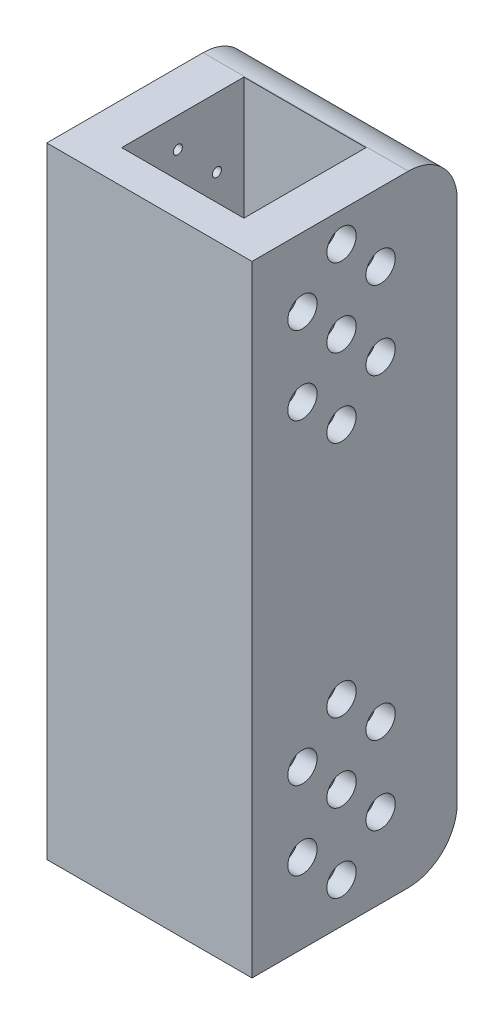
SolidWorks part; units mm, degrees
ref_plane "Front Plane" through (0, 0, 0) normal (0, 0, 1) x (1, 0, 0)
ref_plane "Top Plane" through (0, 0, 0) normal (0, 1, 0) x (1, 0, 0)
ref_plane "Right Plane" through (0, 0, 0) normal (1, 0, 0) x (0, 0, -1)
sketch "Sketch1" plane through (0, 0, 0) normal (0, 1, 0) x (1, 0, 0)
  line L0 (-34.726, 28.4824) -> (-36.316, 28.4824)
  line L1 (-27.816, -6.6876) -> (-2.816, -6.6876)
  line L2 (5.684, 28.4824) -> (4.0937, 28.4824)
  line L3 (-34.726, 25.1424) -> (4.0937, 25.1424)
  line L4 (-27.816, 18.3124) -> (-2.816, 18.3124)
  line L5 (-36.316, 28.4824) -> (-36.316, -13.5176)
  line L6 (-2.816, 18.3124) -> (-2.816, -6.6876)
  line L7 (5.684, -13.5176) -> (-36.316, -13.5176)
  line L8 (4.0937, 28.4824) -> (4.0937, 25.1424)
  line L9 (5.684, 28.4824) -> (5.684, -13.5176)
  line L10 (-34.726, 28.4824) -> (-34.726, 25.1424)
  line L11 (-27.816, -6.6876) -> (-27.816, 18.3124)
  dimension "D1" = 1.5903
  dimension "D2" = 1.59
  dimension "D3" = 3.34
  dimension "D4" = 25
  dimension "D5" = 42
  dimension "D6" = 42
  dimension "D7" = 42
  dimension "D8" = 25
  dimension "D9" = 8.5
  dimension "D10" = 6.83
  dimension "D11" = 6.83
extrude "Boss-Extrude1" add sketch "Sketch1" along normal blind 127
sketch "Sketch3" plane through (-34.726, 0, 0) normal (1, 0, 0) x (0, 0, -1)
  line L0 (25.1424, 127) -> (28.4824, 126.0229)
  line L1 (28.4824, 127) -> (28.4824, 0) construction
  line L2 (28.4824, 126.0229) -> (28.4824, 125.8182)
  line L3 (28.4824, 125.8182) -> (25.1424, 124.83)
  line L4 (25.1424, 127) -> (25.1424, 0) construction
  line L5 (25.1424, 127) -> (25.1424, 124.83)
  line L6 (25.1424, 124.83) -> (28.4824, 123.8529)
  line L7 (28.4824, 123.6482) -> (25.1424, 122.66)
  line L8 (28.4824, 123.8529) -> (28.4824, 123.6482)
  line L9 (25.1424, 124.83) -> (25.1424, 122.66)
  line L10 (25.1424, 122.66) -> (28.4824, 121.6829)
  line L11 (28.4824, 121.4782) -> (25.1424, 120.49)
  line L12 (28.4824, 121.6829) -> (28.4824, 121.4782)
  line L13 (25.1424, 122.66) -> (25.1424, 120.49)
  line L14 (25.1424, 120.49) -> (28.4824, 119.5129)
  line L15 (28.4824, 119.3082) -> (25.1424, 118.32)
  line L16 (28.4824, 119.5129) -> (28.4824, 119.3082)
  line L17 (25.1424, 120.49) -> (25.1424, 118.32)
  line L18 (25.1424, 118.32) -> (28.4824, 117.3429)
  line L19 (28.4824, 117.1382) -> (25.1424, 116.15)
  line L20 (28.4824, 117.3429) -> (28.4824, 117.1382)
  line L21 (25.1424, 118.32) -> (25.1424, 116.15)
  line L22 (25.1424, 116.15) -> (28.4824, 115.1729)
  line L23 (28.4824, 114.9682) -> (25.1424, 113.98)
  line L24 (28.4824, 115.1729) -> (28.4824, 114.9682)
  line L25 (25.1424, 116.15) -> (25.1424, 113.98)
  line L26 (25.1424, 113.98) -> (28.4824, 113.0029)
  line L27 (28.4824, 112.7982) -> (25.1424, 111.81)
  line L28 (28.4824, 113.0029) -> (28.4824, 112.7982)
  line L29 (25.1424, 113.98) -> (25.1424, 111.81)
  line L30 (25.1424, 111.81) -> (28.4824, 110.8329)
  line L31 (28.4824, 110.6282) -> (25.1424, 109.64)
  line L32 (28.4824, 110.8329) -> (28.4824, 110.6282)
  line L33 (25.1424, 111.81) -> (25.1424, 109.64)
  line L34 (25.1424, 109.64) -> (28.4824, 108.6629)
  line L35 (28.4824, 108.4582) -> (25.1424, 107.47)
  line L36 (28.4824, 108.6629) -> (28.4824, 108.4582)
  line L37 (25.1424, 109.64) -> (25.1424, 107.47)
  line L38 (25.1424, 107.47) -> (28.4824, 106.4929)
  line L39 (28.4824, 106.2882) -> (25.1424, 105.3)
  line L40 (28.4824, 106.4929) -> (28.4824, 106.2882)
  line L41 (25.1424, 107.47) -> (25.1424, 105.3)
  line L42 (25.1424, 105.3) -> (28.4824, 104.3229)
  line L43 (28.4824, 104.1182) -> (25.1424, 103.13)
  line L44 (28.4824, 104.3229) -> (28.4824, 104.1182)
  line L45 (25.1424, 105.3) -> (25.1424, 103.13)
  line L46 (25.1424, 103.13) -> (28.4824, 102.1529)
  line L47 (28.4824, 101.9482) -> (25.1424, 100.96)
  line L48 (28.4824, 102.1529) -> (28.4824, 101.9482)
  line L49 (25.1424, 103.13) -> (25.1424, 100.96)
  line L50 (25.1424, 100.96) -> (28.4824, 99.9829)
  line L51 (28.4824, 99.7782) -> (25.1424, 98.79)
  line L52 (28.4824, 99.9829) -> (28.4824, 99.7782)
  line L53 (25.1424, 100.96) -> (25.1424, 98.79)
  line L54 (25.1424, 98.79) -> (28.4824, 97.8129)
  line L55 (28.4824, 97.6082) -> (25.1424, 96.62)
  line L56 (28.4824, 97.8129) -> (28.4824, 97.6082)
  line L57 (25.1424, 98.79) -> (25.1424, 96.62)
  line L58 (25.1424, 96.62) -> (28.4824, 95.6429)
  line L59 (28.4824, 95.4382) -> (25.1424, 94.45)
  line L60 (28.4824, 95.6429) -> (28.4824, 95.4382)
  line L61 (25.1424, 96.62) -> (25.1424, 94.45)
  line L62 (25.1424, 94.45) -> (28.4824, 93.4729)
  line L63 (28.4824, 93.2682) -> (25.1424, 92.28)
  line L64 (28.4824, 93.4729) -> (28.4824, 93.2682)
  line L65 (25.1424, 94.45) -> (25.1424, 92.28)
  line L66 (25.1424, 92.28) -> (28.4824, 91.3029)
  line L67 (28.4824, 91.0982) -> (25.1424, 90.11)
  line L68 (28.4824, 91.3029) -> (28.4824, 91.0982)
  line L69 (25.1424, 92.28) -> (25.1424, 90.11)
  line L70 (25.1424, 90.11) -> (28.4824, 89.1329)
  line L71 (28.4824, 88.9282) -> (25.1424, 87.94)
  line L72 (28.4824, 89.1329) -> (28.4824, 88.9282)
  line L73 (25.1424, 90.11) -> (25.1424, 87.94)
  line L74 (25.1424, 87.94) -> (28.4824, 86.9629)
  line L75 (28.4824, 86.7582) -> (25.1424, 85.77)
  line L76 (28.4824, 86.9629) -> (28.4824, 86.7582)
  line L77 (25.1424, 87.94) -> (25.1424, 85.77)
  line L78 (25.1424, 85.77) -> (28.4824, 84.7929)
  line L79 (28.4824, 84.5882) -> (25.1424, 83.6)
  line L80 (28.4824, 84.7929) -> (28.4824, 84.5882)
  line L81 (25.1424, 85.77) -> (25.1424, 83.6)
  line L82 (25.1424, 83.6) -> (28.4824, 82.6229)
  line L83 (28.4824, 82.4182) -> (25.1424, 81.43)
  line L84 (28.4824, 82.6229) -> (28.4824, 82.4182)
  line L85 (25.1424, 83.6) -> (25.1424, 81.43)
  line L86 (25.1424, 81.43) -> (28.4824, 80.4529)
  line L87 (28.4824, 80.2482) -> (25.1424, 79.26)
  line L88 (28.4824, 80.4529) -> (28.4824, 80.2482)
  line L89 (25.1424, 81.43) -> (25.1424, 79.26)
  line L90 (25.1424, 79.26) -> (28.4824, 78.2829)
  line L91 (28.4824, 78.0782) -> (25.1424, 77.09)
  line L92 (28.4824, 78.2829) -> (28.4824, 78.0782)
  line L93 (25.1424, 79.26) -> (25.1424, 77.09)
  line L94 (25.1424, 77.09) -> (28.4824, 76.1129)
  line L95 (28.4824, 75.9082) -> (25.1424, 74.92)
  line L96 (28.4824, 76.1129) -> (28.4824, 75.9082)
  line L97 (25.1424, 77.09) -> (25.1424, 74.92)
  line L98 (25.1424, 74.92) -> (28.4824, 73.9429)
  line L99 (28.4824, 73.7382) -> (25.1424, 72.75)
  line L100 (28.4824, 73.9429) -> (28.4824, 73.7382)
  line L101 (25.1424, 74.92) -> (25.1424, 72.75)
  line L102 (25.1424, 72.75) -> (28.4824, 71.7729)
  line L103 (28.4824, 71.5682) -> (25.1424, 70.58)
  line L104 (28.4824, 71.7729) -> (28.4824, 71.5682)
  line L105 (25.1424, 72.75) -> (25.1424, 70.58)
  line L106 (25.1424, 70.58) -> (28.4824, 69.6029)
  line L107 (28.4824, 69.3982) -> (25.1424, 68.41)
  line L108 (28.4824, 69.6029) -> (28.4824, 69.3982)
  line L109 (25.1424, 70.58) -> (25.1424, 68.41)
  line L110 (25.1424, 68.41) -> (28.4824, 67.4329)
  line L111 (28.4824, 67.2282) -> (25.1424, 66.24)
  line L112 (28.4824, 67.4329) -> (28.4824, 67.2282)
  line L113 (25.1424, 68.41) -> (25.1424, 66.24)
  line L114 (25.1424, 66.24) -> (28.4824, 65.2629)
  line L115 (28.4824, 65.0582) -> (25.1424, 64.07)
  line L116 (28.4824, 65.2629) -> (28.4824, 65.0582)
  line L117 (25.1424, 66.24) -> (25.1424, 64.07)
  line L118 (25.1424, 64.07) -> (28.4824, 63.0929)
  line L119 (28.4824, 62.8882) -> (25.1424, 61.9)
  line L120 (28.4824, 63.0929) -> (28.4824, 62.8882)
  line L121 (25.1424, 64.07) -> (25.1424, 61.9)
  line L122 (25.1424, 61.9) -> (28.4824, 60.9229)
  line L123 (28.4824, 60.7182) -> (25.1424, 59.73)
  line L124 (28.4824, 60.9229) -> (28.4824, 60.7182)
  line L125 (25.1424, 61.9) -> (25.1424, 59.73)
  line L126 (25.1424, 59.73) -> (28.4824, 58.7529)
  line L127 (28.4824, 58.5482) -> (25.1424, 57.56)
  line L128 (28.4824, 58.7529) -> (28.4824, 58.5482)
  line L129 (25.1424, 59.73) -> (25.1424, 57.56)
  line L130 (25.1424, 57.56) -> (28.4824, 56.5829)
  line L131 (28.4824, 56.3782) -> (25.1424, 55.39)
  line L132 (28.4824, 56.5829) -> (28.4824, 56.3782)
  line L133 (25.1424, 57.56) -> (25.1424, 55.39)
  line L134 (25.1424, 55.39) -> (28.4824, 54.4129)
  line L135 (28.4824, 54.2082) -> (25.1424, 53.22)
  line L136 (28.4824, 54.4129) -> (28.4824, 54.2082)
  line L137 (25.1424, 55.39) -> (25.1424, 53.22)
  line L138 (25.1424, 53.22) -> (28.4824, 52.2429)
  line L139 (28.4824, 52.0382) -> (25.1424, 51.05)
  line L140 (28.4824, 52.2429) -> (28.4824, 52.0382)
  line L141 (25.1424, 53.22) -> (25.1424, 51.05)
  line L142 (25.1424, 51.05) -> (28.4824, 50.0729)
  line L143 (28.4824, 49.8682) -> (25.1424, 48.88)
  line L144 (28.4824, 50.0729) -> (28.4824, 49.8682)
  line L145 (25.1424, 51.05) -> (25.1424, 48.88)
  line L146 (25.1424, 48.88) -> (28.4824, 47.9029)
  line L147 (28.4824, 47.6982) -> (25.1424, 46.71)
  line L148 (28.4824, 47.9029) -> (28.4824, 47.6982)
  line L149 (25.1424, 48.88) -> (25.1424, 46.71)
  line L150 (25.1424, 46.71) -> (28.4824, 45.7329)
  line L151 (28.4824, 45.5282) -> (25.1424, 44.54)
  line L152 (28.4824, 45.7329) -> (28.4824, 45.5282)
  line L153 (25.1424, 46.71) -> (25.1424, 44.54)
  line L154 (25.1424, 44.54) -> (28.4824, 43.5629)
  line L155 (28.4824, 43.3582) -> (25.1424, 42.37)
  line L156 (28.4824, 43.5629) -> (28.4824, 43.3582)
  line L157 (25.1424, 44.54) -> (25.1424, 42.37)
  line L158 (25.1424, 42.37) -> (28.4824, 41.3929)
  line L159 (28.4824, 41.1882) -> (25.1424, 40.2)
  line L160 (28.4824, 41.3929) -> (28.4824, 41.1882)
  line L161 (25.1424, 42.37) -> (25.1424, 40.2)
  line L162 (25.1424, 40.2) -> (28.4824, 39.2229)
  line L163 (28.4824, 39.0182) -> (25.1424, 38.03)
  line L164 (28.4824, 39.2229) -> (28.4824, 39.0182)
  line L165 (25.1424, 40.2) -> (25.1424, 38.03)
  line L166 (25.1424, 38.03) -> (28.4824, 37.0529)
  line L167 (28.4824, 36.8482) -> (25.1424, 35.86)
  line L168 (28.4824, 37.0529) -> (28.4824, 36.8482)
  line L169 (25.1424, 38.03) -> (25.1424, 35.86)
  line L170 (25.1424, 35.86) -> (28.4824, 34.8829)
  line L171 (28.4824, 34.6782) -> (25.1424, 33.69)
  line L172 (28.4824, 34.8829) -> (28.4824, 34.6782)
  line L173 (25.1424, 35.86) -> (25.1424, 33.69)
  line L174 (25.1424, 33.69) -> (28.4824, 32.7129)
  line L175 (28.4824, 32.5082) -> (25.1424, 31.52)
  line L176 (28.4824, 32.7129) -> (28.4824, 32.5082)
  line L177 (25.1424, 33.69) -> (25.1424, 31.52)
  line L178 (25.1424, 31.52) -> (28.4824, 30.5429)
  line L179 (28.4824, 30.3382) -> (25.1424, 29.35)
  line L180 (28.4824, 30.5429) -> (28.4824, 30.3382)
  line L181 (25.1424, 31.52) -> (25.1424, 29.35)
  line L182 (25.1424, 29.35) -> (28.4824, 28.3729)
  line L183 (28.4824, 28.1682) -> (25.1424, 27.18)
  line L184 (28.4824, 28.3729) -> (28.4824, 28.1682)
  line L185 (25.1424, 29.35) -> (25.1424, 27.18)
  line L186 (25.1424, 27.18) -> (28.4824, 26.2029)
  line L187 (28.4824, 25.9982) -> (25.1424, 25.01)
  line L188 (28.4824, 26.2029) -> (28.4824, 25.9982)
  line L189 (25.1424, 27.18) -> (25.1424, 25.01)
  line L190 (25.1424, 25.01) -> (28.4824, 24.0329)
  line L191 (28.4824, 23.8282) -> (25.1424, 22.84)
  line L192 (28.4824, 24.0329) -> (28.4824, 23.8282)
  line L193 (25.1424, 25.01) -> (25.1424, 22.84)
  line L194 (25.1424, 22.84) -> (28.4824, 21.8629)
  line L195 (28.4824, 21.6582) -> (25.1424, 20.67)
  line L196 (28.4824, 21.8629) -> (28.4824, 21.6582)
  line L197 (25.1424, 22.84) -> (25.1424, 20.67)
  line L198 (25.1424, 20.67) -> (28.4824, 19.6929)
  line L199 (28.4824, 19.4882) -> (25.1424, 18.5)
  line L200 (28.4824, 19.6929) -> (28.4824, 19.4882)
  line L201 (25.1424, 20.67) -> (25.1424, 18.5)
  line L202 (25.1424, 18.5) -> (28.4824, 17.5229)
  line L203 (28.4824, 17.3182) -> (25.1424, 16.33)
  line L204 (28.4824, 17.5229) -> (28.4824, 17.3182)
  line L205 (25.1424, 18.5) -> (25.1424, 16.33)
  line L206 (25.1424, 16.33) -> (28.4824, 15.3529)
  line L207 (28.4824, 15.1482) -> (25.1424, 14.16)
  line L208 (28.4824, 15.3529) -> (28.4824, 15.1482)
  line L209 (25.1424, 16.33) -> (25.1424, 14.16)
  line L210 (25.1424, 14.16) -> (28.4824, 13.1829)
  line L211 (28.4824, 12.9782) -> (25.1424, 11.99)
  line L212 (28.4824, 13.1829) -> (28.4824, 12.9782)
  line L213 (25.1424, 14.16) -> (25.1424, 11.99)
  line L214 (25.1424, 11.99) -> (28.4824, 11.0129)
  line L215 (28.4824, 10.8082) -> (25.1424, 9.82)
  line L216 (28.4824, 11.0129) -> (28.4824, 10.8082)
  line L217 (25.1424, 11.99) -> (25.1424, 9.82)
  line L218 (25.1424, 9.82) -> (28.4824, 8.8429)
  line L219 (28.4824, 8.6382) -> (25.1424, 7.65)
  line L220 (28.4824, 8.8429) -> (28.4824, 8.6382)
  line L221 (25.1424, 9.82) -> (25.1424, 7.65)
  line L222 (25.1424, 7.65) -> (28.4824, 6.6729)
  line L223 (28.4824, 6.4682) -> (25.1424, 5.48)
  line L224 (28.4824, 6.6729) -> (28.4824, 6.4682)
  line L225 (25.1424, 7.65) -> (25.1424, 5.48)
  line L226 (25.1424, 5.48) -> (28.4824, 4.5029)
  line L227 (28.4824, 4.2982) -> (25.1424, 3.31)
  line L228 (28.4824, 4.5029) -> (28.4824, 4.2982)
  line L229 (25.1424, 5.48) -> (25.1424, 3.31)
  line L230 (25.1424, 3.31) -> (28.4824, 2.3329)
  line L231 (28.4824, 2.1282) -> (25.1424, 1.14)
  line L232 (28.4824, 2.3329) -> (28.4824, 2.1282)
  line L233 (25.1424, 3.31) -> (25.1424, 1.14)
  line L234 (25.1424, 1.14) -> (28.4824, 0.1629)
  line L235 (28.4824, 0.1629) -> (28.4824, 0)
  line L236 (28.4824, 0) -> (25.1424, 0)
  line L237 (25.1424, 0) -> (25.1424, 1.14)
  line L238 (28.4824, -0.0418) -> (25.1424, -1.03) [skipped]
  line L239 (25.1424, 1.14) -> (25.1424, -1.03) [skipped]
  line L240 (28.4824, 0.1629) -> (28.4824, -0.0418) [skipped]
  dimension "D1" = 3.4831
  dimension "D2" = 3.48
  dimension "D3" = 2.17
  dimension "D4" = 59
extrude "Boss-Extrude2" add sketch "Sketch3" along normal up to surface (38.8197 mm away) contours L231 L229 L230 | L227 L229 L226 L230 | L223 L229 L222 L230 | L234 L230 L5 L229 | L211 L229 L210 L230 | L207 L229 L206 L230 | L203 L229 L202 L230 | L199 L229 L198 L230 | L183 L229 L182 L230 | L171 L229 L170 L230 | L167 L229 L166 L230 | L159 L229 L158 L230 | L155 L229 L154 L230 | L147 L229 L146 L230 | L143 L229 L142 L230 | L139 L229 L138 L230 | L135 L229 L134 L230 | L131 L229 L130 L230 | L111 L229 L110 L230 | L107 L229 L106 L230 | L95 L229 L94 L230 | L91 L229 L90 L230 | L87 L229 L86 L230 | L71 L229 L70 L230 | L67 L229 L66 L230 | L63 L229 L62 L230 | L59 L229 L58 L230 | L55 L229 L54 L230 | L51 L229 L50 L230 | L47 L229 L46 L230 | L43 L229 L42 L230 | L31 L229 L30 L230 | L27 L229 L26 L230 | L23 L229 L22 L230 | L19 L229 L18 L230 | L15 L229 L14 L230 | L11 L229 L10 L230 | L7 L229 L6 L230 | L3 L229 L0 L230 | L234 L235 L236 L237 | L218 L220 L219 L221 | L214 L216 L215 L217 | L195 L197 L194 L196 | L190 L192 L191 L193 | L186 L188 L187 L189 | L179 L181 L178 L180 | L175 L177 L174 L176 | L162 L164 L163 L165 | L151 L153 L150 L152 | L129 L127 L128 L126 | L122 L124 L123 L125 | L118 L120 L119 L121 | L114 L116 L115 L117 | L103 L105 L102 L104 | L99 L101 L98 L100 | L82 L84 L83 L85 | L78 L80 L79 L81 | L74 L76 L75 L77 | L39 L41 L38 L40 | L35 L37 L34 L36 region at (-34.726, 0.3868, -26.3949) region at (-34.726, 2.227, -26.3517) region at (-34.726, 4.397, -26.3517) region at (-34.726, 6.567, -26.3517) region at (-34.726, 13.077, -26.3517) region at (-34.726, 15.247, -26.3517) region at (-34.726, 17.417, -26.3517) region at (-34.726, 19.587, -26.3517) region at (-34.726, 28.267, -26.3517) region at (-34.726, 34.777, -26.3517) region at (-34.726, 36.947, -26.3517) region at (-34.726, 41.287, -26.3517) region at (-34.726, 43.457, -26.3517) region at (-34.726, 47.797, -26.3517) region at (-34.726, 49.967, -26.3517) region at (-34.726, 52.137, -26.3517) region at (-34.726, 54.307, -26.3517) region at (-34.726, 56.477, -26.3517) region at (-34.726, 67.327, -26.3517) region at (-34.726, 69.497, -26.3517) region at (-34.726, 76.007, -26.3517) region at (-34.726, 78.177, -26.3517) region at (-34.726, 80.347, -26.3517) region at (-34.726, 89.027, -26.3517) region at (-34.726, 91.197, -26.3517) region at (-34.726, 93.367, -26.3517) region at (-34.726, 95.537, -26.3517) region at (-34.726, 97.707, -26.3517) region at (-34.726, 99.877, -26.3517) region at (-34.726, 102.047, -26.3517) region at (-34.726, 104.217, -26.3517) region at (-34.726, 110.727, -26.3517) region at (-34.726, 112.897, -26.3517) region at (-34.726, 115.067, -26.3517) region at (-34.726, 117.237, -26.3517) region at (-34.726, 119.407, -26.3517) region at (-34.726, 121.577, -26.3517) region at (-34.726, 123.747, -26.3517) region at (-34.726, 125.917, -26.3517) up to face at (4.0937, 63.5, -26.8124)
fillet "Fillet1" radius 10 1 edges at (-15.316, 0, -28.4824)
fillet "Fillet2" radius 10 1 edges at (4.8889, 127, -28.4824)
sketch "Sketch6" plane through (-36.316, 0, 0) normal (-1, 0, 0) x (0, 0, 1)
  circle A0 centre (-4.8037, 120.9136) radius 1.85
  circle A1 centre (3.1937, 112.9163) radius 1.85
  circle A2 centre (-4.8037, 104.9189) radius 1.85
  circle A3 centre (-12.8011, 112.9163) radius 1.85
  circle A4 centre (3.1937, 96.9163) radius 1.85
  circle A5 centre (-4.8037, 88.9189) radius 1.85
  circle A6 centre (-12.8011, 96.9163) radius 1.85
  circle A7 centre (3.1937, 80.9163) radius 1.85
  circle A8 centre (-4.8037, 72.9189) radius 1.85
  circle A9 centre (-12.8011, 80.9163) radius 1.85
  circle A10 centre (3.1937, 64.9163) radius 1.85
  circle A11 centre (-4.8037, 56.9189) radius 1.85
  circle A12 centre (-12.8011, 64.9163) radius 1.85
  circle A14 centre (-4.8037, 40.9189) radius 1.85
  circle A16 centre (3.1937, 32.9163) radius 1.85
  circle A17 centre (-4.8037, 24.9189) radius 1.85
  circle A18 centre (-12.8011, 32.9163) radius 1.85
  circle A19 centre (3.1937, 16.9163) radius 1.85
  circle A20 centre (-4.8037, 8.9189) radius 1.85
  circle A21 centre (-12.8011, 16.9163) radius 1.85
  circle A22 centre (3.1937, 48.9163) radius 1.85
  circle A23 centre (-12.8011, 48.9163) radius 1.85
  dimension "D1" = 11.31
  dimension "D3" = 7
  dimension "D2" = 11.31
hole_wizard "CBORE for #00 Binding Head Machine Screw2" positions "Sketch8" profile "Sketch7" counterbore size "#00" standard "ANSI Inch" end condition through all
sketch "Sketch8" plane through (-36.316, 0, 0) normal (-1, 0, 0) x (0, 0, 1)
  point P0 (-12.8011, 112.9163)
  point P3 (-4.8037, 120.9136)
  point P6 (3.1937, 112.9163)
  point P9 (-4.8037, 104.9189)
  point P12 (-4.8037, 40.9189)
  point P15 (-12.8011, 32.9163)
  point P18 (-12.8011, 16.9163)
  point P21 (-12.8011, 96.9163)
  point P24 (-4.8037, 88.9189)
  point P27 (3.1937, 96.9163)
  point P30 (-4.8037, 24.9189)
  point P33 (-4.8037, 8.9189)
  point P36 (3.1937, 16.9163)
  point P39 (3.1937, 32.9163)
sketch "Sketch7" plane through (-36.316, 112.9163, -12.8011) normal (0, 1, 0) x (0, 0, 1)
  line L0 (0, 0) -> (0, 42)
  line L1 (0, 42) -> (0.6604, 42)
  line L3 (0.6604, 42) -> (0.6604, 3)
  line L4 (0.6604, 3) -> (3, 3)
  line L5 (3, 3) -> (3, 0)
  line L7 (3, 0) -> (0, 0)
  line L11 (0, -6.35) -> (0, 107.95) construction
  dimension "Thru Hole Dia." = 1.3208
  dimension "Thru Hole Depth" = 42
  dimension "C'Bore Dia." = 6
  dimension "C'Bore Depth" = 3
hole_wizard "CBORE for M5 Hex Head Bolt1" positions "Sketch11" profile "Sketch10" counterbore size "M5" standard "ANSI Metric" end condition through all
sketch "Sketch11" plane through (5.684, 0, 0) normal (1, 0, 0) x (0, 0, -1)
  circle A0 centre (4.8037, 8.9189) radius 0.6604 construction
  circle A1 centre (-3.1937, 16.9163) radius 0.6604 construction
  circle A2 centre (-3.1937, 32.9163) radius 0.6604 construction
  circle A3 centre (4.8037, 40.9189) radius 0.6604 construction
  circle A4 centre (12.8011, 32.9163) radius 0.6604 construction
  circle A5 centre (4.8037, 24.9189) radius 0.6604 construction
  circle A6 centre (12.8011, 16.9163) radius 0.6604 construction
  point P0 (12.8011, 112.9163)
  point P3 (4.8037, 120.9136)
  point P6 (4.8037, 104.9189)
  point P9 (-3.1937, 112.9163)
  point P12 (-3.1937, 96.9163)
  point P15 (12.8011, 96.9163)
  point P18 (4.8037, 88.9189)
  point P21 (4.8037, 8.2585)
  point P25 (-3.1937, 16.2559)
  point P29 (-3.1937, 32.2559)
  point P33 (4.8037, 40.2585)
  point P37 (12.8011, 32.2559)
  point P41 (4.8037, 24.2585)
  point P45 (12.8011, 16.2559)
sketch "Sketch10" plane through (5.684, 112.9163, -12.8011) normal (0, 1, 0) x (0, 0, -1)
  line L0 (0, 0) -> (0, 42)
  line L1 (0, 42) -> (0.925, 42)
  line L3 (0.925, 42) -> (0.925, 4)
  line L4 (0.925, 4) -> (3, 4)
  line L5 (3, 4) -> (3, 0)
  line L7 (3, 0) -> (0, 0)
  line L11 (0, -6.35) -> (0, 107.95) construction
  dimension "Thru Hole Dia." = 1.85
  dimension "Thru Hole Depth" = 42
  dimension "C'Bore Dia." = 6
  dimension "C'Bore Depth" = 4
